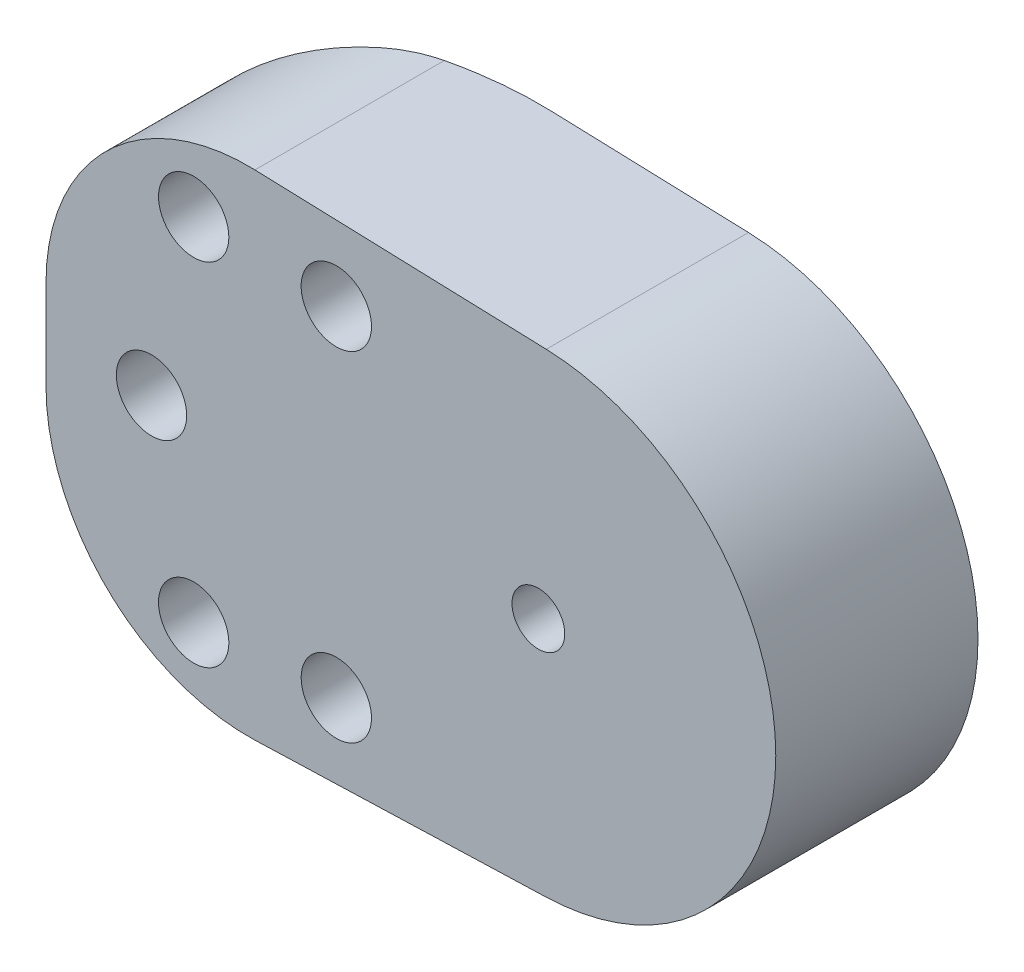
SolidWorks part; units mm, degrees
ref_plane "Alzado" through (0, 0, 0) normal (0, 0, 1) x (1, 0, 0)
ref_plane "Planta" through (0, 0, 0) normal (0, 1, 0) x (1, 0, 0)
ref_plane "Vista lateral" through (0, 0, 0) normal (1, 0, 0) x (0, 0, -1)
sketch "Croquis1" plane through (0, 0, 0) normal (0, 0, 1) x (1, 0, 0)
  line L0 (-45, 15) -> (0.4475, 13.4926)
  line L1 (-45, 0) -> (0, 0) construction
  line L2 (-45, 15) -> (-45, 0) construction
  line L3 (-28, -14.4361) -> (-28, 14.4361)
  line L4 (0, 0) -> (0, -13.5) construction
  line L5 (-45, -15) -> (0.4475, -13.4926)
  circle A0 centre (0, 0) radius 13.5
  point P13 (-28, 0)
  dimension "D1" = 27
  dimension "D2" = 45
  dimension "D3" = 15
  dimension "D4" = 28
extrude "Saliente-Extruir1" add sketch "Croquis1" along normal blind 11.5 contours A0 L0 L3 L5 | A0 region at (-19.0166, 0, 0) region at (0, 0, 0)
sketch "Croquis3" plane through (0, 0, 11.5) normal (0, 0, 1) x (1, 0, 0)
  line L0 (0, 0) -> (-22, 0) construction
  line L1 (0, 0) -> (-19.6021, 9.9878) construction
  line L2 (0, 0) -> (-11.4907, 9.6418) construction
  circle A0 centre (-22, 0) radius 2
  circle A1 centre (-19.6021, 9.9878) radius 2
  circle A2 centre (-11.4907, 9.6418) radius 2
  circle A3 centre (-19.6021, -9.9878) radius 2
  circle A4 centre (-11.4907, -9.6418) radius 2
  dimension "D2" = 4
  dimension "D4" = 27
  dimension "D1" = 22
  dimension "D3" = 22
  dimension "D5" = 15
  dimension "D6" = 40
extrude "Cortar-Extruir1" cut sketch "Croquis3" against normal through all
sketch "Croquis4" plane through (0, 0, 0) normal (0, 1, 0) x (1, 0, 0)
  line L0 (0, 0) -> (0, -11.5) construction
  line L1 (-28, -11.5) -> (0.4475, -11.5) construction
  line L2 (0, -5.75) -> (-15, -5.75) construction
  line L3 (-15, -5.75) -> (-15, 0) construction
  line L4 (-28, 0) -> (0.4475, 0) construction
  line L5 (-15, 0) -> (-28, -5.75)
  line L6 (-28, -11.5) -> (-28, 0) construction
  line L7 (-28, -5.75) -> (-28, 0)
  line L8 (-28, 0) -> (-15, 0)
  dimension "D1" = 15
extrude "Cortar-Extruir2" cut sketch "Croquis4" against normal through all both and the other way through all
fillet "Redondeo1" radius 20 1 edges at (-15, 0, 0)
fillet "Redondeo2" radius 11.5 2 edges at (-28, 14.4361, 8.625) (-28, -14.4361, 8.625)
sketch "Croquis5" plane through (0, 0, 0) normal (0, 0, -1) x (-1, 0, 0)
  circle A0 centre (0, 0) radius 6
  dimension "D1" = 12
extrude "Cortar-Extruir3" cut sketch "Croquis5" against normal blind 7
sketch "Croquis6" plane through (0, 0, 0) normal (0, 0, -1) x (-1, 0, 0)
  circle A0 centre (0, 0) radius 9.5
  dimension "D1" = 19
extrude "Cortar-Extruir4" cut sketch "Croquis6" against normal blind 5
sketch "Croquis7" plane through (0, 0, 7) normal (0, 0, -1) x (-1, 0, 0)
  circle A0 centre (0, 0) radius 1.5
  dimension "D1" = 3
extrude "Cortar-Extruir5" cut sketch "Croquis7" against normal through all
